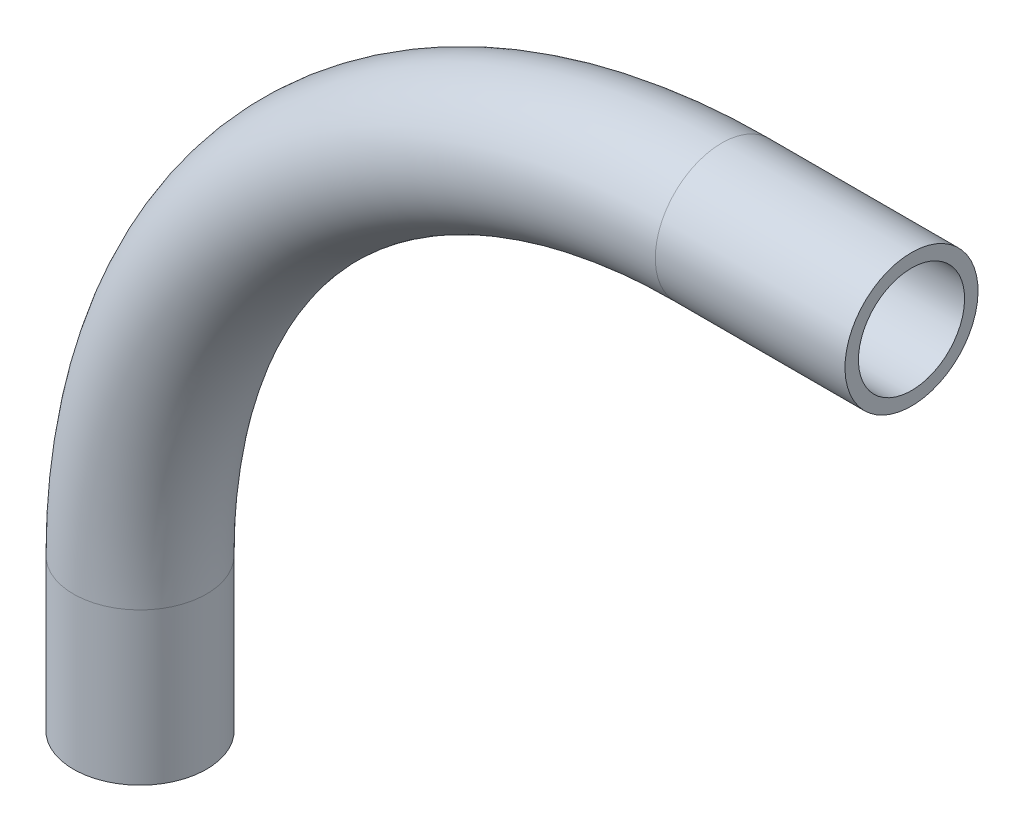
SolidWorks part; units mm, degrees
material "PVC Rigid"
ref_plane "front" through (0, 0, 0) normal (0, 0, 1) x (1, 0, 0)
ref_plane "top" through (0, 0, 0) normal (0, 1, 0) x (1, 0, 0)
ref_plane "side" through (0, 0, 0) normal (1, 0, 0) x (0, 0, -1)
sketch "ElbowArc" plane through (0, 0, 0) normal (0, 0, 1) x (1, 0, 0)
  arc A0 (-146.05, 0) -> (0, 146.05) centre (0, 0) cw
  dimension "BendAngle" = 90
  dimension "BendRadius" = 146.05
sketch "Route" plane through (0, 0, 0) normal (0, 1, 0) x (1, 0, 0)
  circle A0 centre (-146.05, 0) radius 16.7005
  dimension "ElbowOD" = 33.401
  dimension "BendRadius" = 146.05
sweep "Elbow" add profiles "Route" path "ElbowArc"
shell "ElbowShell" thickness 3.3782 removed face at (0, 146.05, 16.7005) removed face at (-146.05, 0, 16.7005)
sketch3d "3DSketch1"
  circle A0 centre (0, 146.05, 0) radius 13.3223 construction
  circle A1 centre (-146.05, 0, 0) radius 16.7005 construction
  circle A2 centre (0, 146.05, 0) radius 13.3223 construction
  point P4 (-146.05, 0, 0)
  point P7 (-146.05, 16.7005, 0)
  point P14 (13.3223, 146.05, 0)
  point P16 (13.3223, 146.05, 0)
ref_plane "Plane1" through (0, 0, 0) normal (1, 0, 0) x (0, 0, -1)
ref_plane "Plane2" through (0, 0, 0) normal (0, -1, 0) x (1, 0, 0)
sketch "Sketch2" plane through (0, 0, 0) normal (1, 0, 0) x (0, 0, -1)
  circle A0 centre (0, 146.05) radius 16.7005 construction
  circle A1 centre (0, 146.05) radius 13.3223 construction
  circle A2 centre (0, 146.05) radius 16.7005
  circle A3 centre (0, 146.05) radius 13.3223
extrude "ElbowExtension-Extrude1" add sketch "Sketch2" along normal blind 47.625
sketch "Sketch3" plane through (0, 0, 0) normal (0, -1, 0) x (1, 0, 0)
  circle A0 centre (-146.05, 0) radius 13.3223 construction
  circle A1 centre (-146.05, 0) radius 16.7005 construction
  circle A2 centre (-146.05, 0) radius 13.3223
  circle A3 centre (-146.05, 0) radius 16.7005
extrude "ElbowExtension-Extrude2" add sketch "Sketch3" along normal blind 38.1
sketch "Sketch4" plane through (0, 0, 0) normal (1, 0, 0) x (0, 0, -1)
  point P0 (0, 146.05)
sketch "Sketch5" plane through (0, 0, 0) normal (0, -1, 0) x (1, 0, 0)
  point P0 (-146.05, 0)
other "CPoint1" parameters "Diameter"=25.4, "StubLength"=0
ref_axis "Axis1" through (10, 146.05, 0) along (-1, 0, 0)
other "CPoint2" parameters "Diameter"=25.4, "StubLength"=0
ref_axis "Axis2" through (-146.05, -10, 0) along (0, 1, 0)
other "RPoint1"
